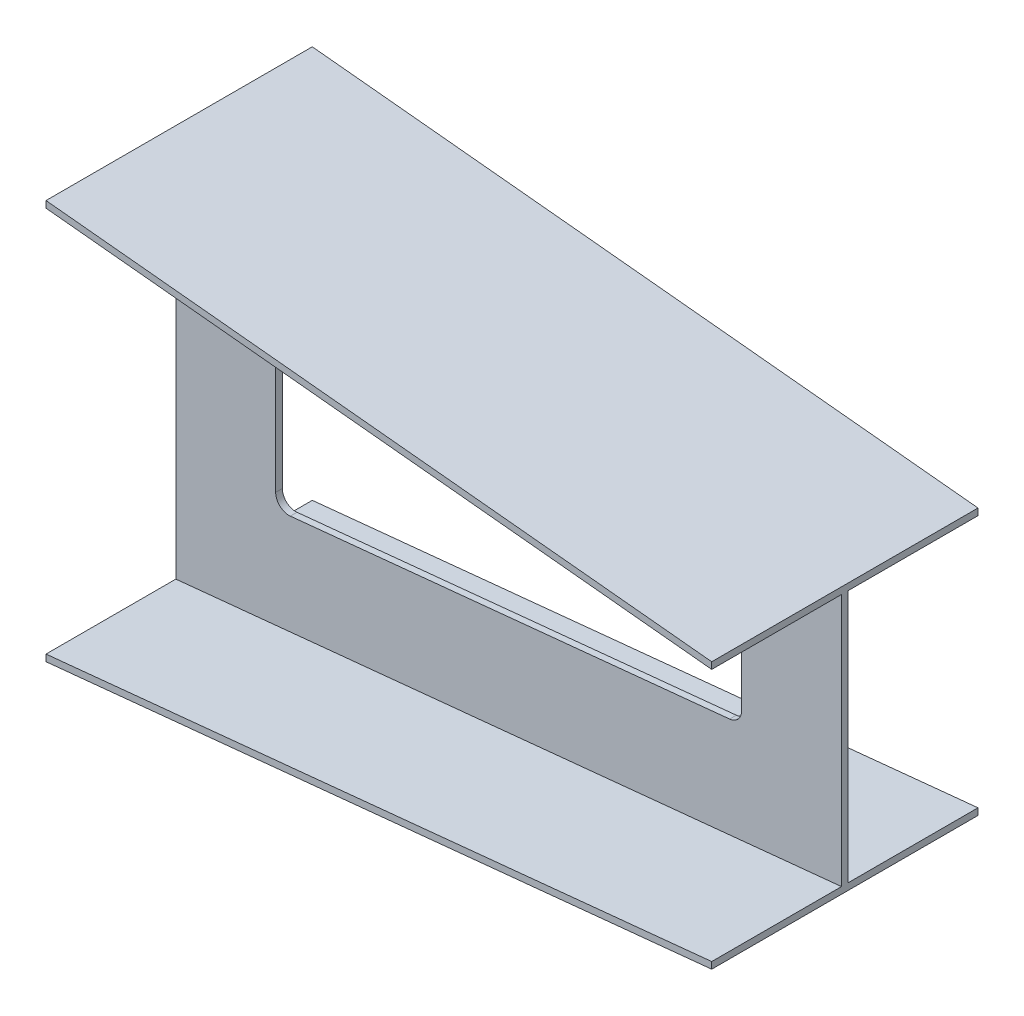
SolidWorks part; units mm, degrees
ref_plane "Front Plane" through (0, 0, 0) normal (0, 0, 1) x (1, 0, 0)
ref_plane "Top Plane" through (0, 0, 0) normal (0, 1, 0) x (1, 0, 0)
ref_plane "Right Plane" through (0, 0, 0) normal (1, 0, 0) x (0, 0, -1)
sketch "Sketch1" plane through (0, 0, 0) normal (1, 0, 0) x (0, 0, -1)
  line L1 (-205, 300) -> (195, 300)
  line L2 (-205, 300) -> (-205, 290)
  line L4 (195, 300) -> (195, 290)
  line L6 (-205, -290) -> (-205, -300)
  line L7 (-205, -300) -> (195, -300)
  line L8 (195, -290) -> (195, -300)
  line L15 (-205, -290) -> (-10, -290)
  line L16 (-5, 290) -> (-5, -690) construction
  line L18 (-205, 290) -> (-10, 290)
  line L19 (0, 0) -> (192.2403, 0) construction
  line L21 (-10, 290) -> (-10, -290)
  line L23 (0, 290) -> (0, -290)
  line L27 (0, 290) -> (195, 290)
  line L28 (0, -290) -> (195, -290)
  dimension "D1" = 400
  dimension "D2" = 10
  dimension "D3" = 600
  dimension "D4" = 10
ref_plane "Plane2" through (1000, 0, 0) normal (1, 0, 0) x (0, 0, -1)
sketch "Sketch4" plane through (1000, 0, -1000) normal (-1, 0, 0) x (0, 0, 1)
  line L1 (805, 200) -> (1205, 200)
  line L2 (805, 200) -> (805, 190)
  line L4 (1205, 200) -> (1205, 190)
  line L6 (805, -190) -> (805, -200)
  line L7 (805, -200) -> (1205, -200)
  line L8 (1205, -190) -> (1205, -200)
  line L15 (805, -190) -> (1000, -190)
  line L16 (1005, 390) -> (1005, -390) construction
  line L18 (805, 190) -> (1000, 190)
  line L19 (1010, -190) -> (1205, -190)
  line L21 (1000, 190) -> (1000, -190)
  line L23 (1010, 190) -> (1010, -190)
  line L24 (1010, 190) -> (1205, 190)
  line L26 (1010, 290) -> (1010, -290) construction
  line L27 (1000, 0) -> (820.2065, 0) construction
  dimension "D1" = 400
  dimension "D2" = 10
  dimension "D3" = 400
  dimension "D4" = 10
loft "Loft4" add profiles "Sketch1", "Sketch4" connector at (0, 290, 10) connector at (1000, 190, 10)
sketch "Sketch6" plane through (0, 0, 10) normal (0, 0, 1) x (1, 0, 0)
  line L8 (150, -124.2519) -> (850, -54.2519)
  line L9 (850, -54.2519) -> (850, 54.2519)
  line L10 (850, 54.2519) -> (150, 124.2519)
  line L11 (150, 124.2519) -> (150, -124.2519)
  line L12 (171.9901, -122.0529) -> (831.9901, -56.0529)
  line L13 (850, -36.1521) -> (850, 36.1521)
  line L14 (831.9901, 56.0529) -> (171.9901, 122.0529)
  line L15 (150, 102.1521) -> (150, -102.1521)
  arc A0 (150, -102.1521) -> (171.9901, -122.0529) centre (170, -102.1521) ccw
  arc A1 (850, 36.1521) -> (831.9901, 56.0529) centre (830, 36.1521) ccw
  arc A2 (850, -36.1521) -> (831.9901, -56.0529) centre (830, -36.1521) cw
  arc A3 (150, 102.1521) -> (171.9901, 122.0529) centre (170, 102.1521) cw
  dimension "D2" = 20
  dimension "D1" = 150
extrude "Cut-Extrude1" cut sketch "Sketch6" against normal blind 10
